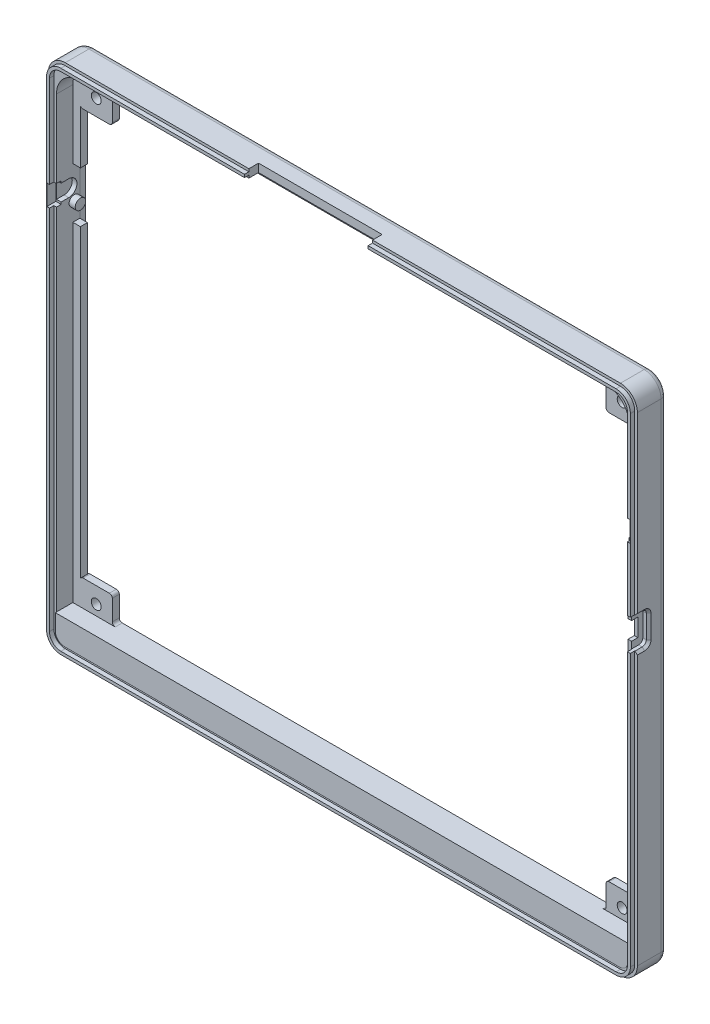
SolidWorks part; units mm, degrees
ref_plane "Спереди" through (0, 0, 0) normal (0, 0, 1) x (1, 0, 0)
ref_plane "Сверху" through (0, 0, 0) normal (0, 1, 0) x (1, 0, 0)
ref_plane "Справа" through (0, 0, 0) normal (1, 0, 0) x (0, 0, -1)
other "Configuration Table"
sketch "Perimeter_shell_profile" plane through (0, 0, 0) normal (0, 0, 1) x (1, 0, 0)
  line L0 (0, -9.8) -> (190, -9.8)
  line L1 (195.8, -4) -> (195.8, 160)
  line L2 (190, 165.8) -> (0, 165.8)
  line L3 (-5.8, 160) -> (-5.8, -4)
  line L4 (0, -7) -> (190, -7)
  line L5 (193, -4) -> (193, 160)
  line L6 (190, 163) -> (0, 163)
  line L7 (-3, 160) -> (-3, -4)
  arc A0 (190, -9.8) -> (195.8, -4) centre (190, -4) ccw
  arc A1 (195.8, 160) -> (190, 165.8) centre (190, 160) ccw
  arc A2 (0, 165.8) -> (-5.8, 160) centre (0, 160) ccw
  arc A3 (-5.8, -4) -> (0, -9.8) centre (0, -4) ccw
  arc A4 (190, -7) -> (193, -4) centre (190, -4) ccw
  arc A5 (193, 160) -> (190, 163) centre (190, 160) ccw
  arc A6 (0, 163) -> (-3, 160) centre (0, 160) ccw
  arc A7 (-3, -4) -> (0, -7) centre (0, -4) ccw
extrude "Perimeter_shell" add sketch "Perimeter_shell_profile" along normal blind 5.6 from offset 7.6 offset against normal yes
sketch "Open_back_frame_profile" plane through (0, 0, 0) normal (0, 0, 1) x (1, 0, 0)
  line L0 (0, -9.8) -> (190, -9.8)
  line L1 (195.8, -4) -> (195.8, 160)
  line L2 (190, 165.8) -> (0, 165.8)
  line L3 (-5.8, 160) -> (-5.8, -4)
  line L4 (1.6, -4.4) -> (188.4, -4.4)
  line L5 (190.4, -2.4) -> (190.4, 158.4)
  line L6 (188.4, 160.4) -> (1.6, 160.4)
  line L7 (-0.4, 158.4) -> (-0.4, -2.4)
  arc A0 (190, -9.8) -> (195.8, -4) centre (190, -4) ccw
  arc A1 (195.8, 160) -> (190, 165.8) centre (190, 160) ccw
  arc A2 (0, 165.8) -> (-5.8, 160) centre (0, 160) ccw
  arc A3 (-5.8, -4) -> (0, -9.8) centre (0, -4) ccw
  arc A4 (188.4, -4.4) -> (190.4, -2.4) centre (188.4, -2.4) ccw
  arc A5 (190.4, 158.4) -> (188.4, 160.4) centre (188.4, 158.4) ccw
  arc A6 (1.6, 160.4) -> (-0.4, 158.4) centre (1.6, 158.4) ccw
  arc A7 (-0.4, -2.4) -> (1.6, -4.4) centre (1.6, -2.4) ccw
extrude "Open_back_frame" add sketch "Open_back_frame_profile" along normal blind 4.5 from offset 12.1 offset against normal yes
sketch "PCB_mount_web_0_profile" plane through (0, 0, 0) normal (0, 0, 1) x (1, 0, 0)
  line L0 (0.5, -6) -> (9.5, -6)
  line L1 (10.5, -5) -> (10.5, 9.5)
  line L2 (9.5, 10.5) -> (0.5, 10.5)
  line L3 (-0.5, 9.5) -> (-0.5, -5)
  arc A0 (9.5, -6) -> (10.5, -5) centre (9.5, -5) ccw
  arc A1 (10.5, 9.5) -> (9.5, 10.5) centre (9.5, 9.5) ccw
  arc A2 (0.5, 10.5) -> (-0.5, 9.5) centre (0.5, 9.5) ccw
  arc A3 (-0.5, -5) -> (0.5, -6) centre (0.5, -5) ccw
extrude "PCB_mount_web_0" add sketch "PCB_mount_web_0_profile" along normal blind 4.5 from offset 12.1 offset against normal yes
sketch "PCB_M3_through_0_profile" plane through (0, 0, 0) normal (0, 0, 1) x (1, 0, 0)
  circle A0 centre (5, 5) radius 1.7
extrude "PCB_M3_through_0" cut sketch "PCB_M3_through_0_profile" against normal blind 4.7 from offset 7.5 offset against normal yes
sketch "PCB_mount_web_1_profile" plane through (0, 0, 0) normal (0, 0, 1) x (1, 0, 0)
  line L0 (180.5, -6) -> (189.5, -6)
  line L1 (190.5, -5) -> (190.5, 9.5)
  line L2 (189.5, 10.5) -> (180.5, 10.5)
  line L3 (179.5, 9.5) -> (179.5, -5)
  arc A0 (189.5, -6) -> (190.5, -5) centre (189.5, -5) ccw
  arc A1 (190.5, 9.5) -> (189.5, 10.5) centre (189.5, 9.5) ccw
  arc A2 (180.5, 10.5) -> (179.5, 9.5) centre (180.5, 9.5) ccw
  arc A3 (179.5, -5) -> (180.5, -6) centre (180.5, -5) ccw
extrude "PCB_mount_web_1" add sketch "PCB_mount_web_1_profile" along normal blind 4.5 from offset 12.1 offset against normal yes
sketch "PCB_M3_through_1_profile" plane through (0, 0, 0) normal (0, 0, 1) x (1, 0, 0)
  circle A0 centre (185, 5) radius 1.7
extrude "PCB_M3_through_1" cut sketch "PCB_M3_through_1_profile" against normal blind 4.7 from offset 7.5 offset against normal yes
sketch "PCB_mount_web_2_profile" plane through (0, 0, 0) normal (0, 0, 1) x (1, 0, 0)
  line L0 (0.5, 149.5) -> (9.5, 149.5)
  line L1 (10.5, 150.5) -> (10.5, 161)
  line L2 (9.5, 162) -> (0.5, 162)
  line L3 (-0.5, 161) -> (-0.5, 150.5)
  arc A0 (9.5, 149.5) -> (10.5, 150.5) centre (9.5, 150.5) ccw
  arc A1 (10.5, 161) -> (9.5, 162) centre (9.5, 161) ccw
  arc A2 (0.5, 162) -> (-0.5, 161) centre (0.5, 161) ccw
  arc A3 (-0.5, 150.5) -> (0.5, 149.5) centre (0.5, 150.5) ccw
extrude "PCB_mount_web_2" add sketch "PCB_mount_web_2_profile" along normal blind 4.5 from offset 12.1 offset against normal yes
sketch "PCB_M3_through_2_profile" plane through (0, 0, 0) normal (0, 0, 1) x (1, 0, 0)
  circle A0 centre (5, 155) radius 1.7
extrude "PCB_M3_through_2" cut sketch "PCB_M3_through_2_profile" against normal blind 4.7 from offset 7.5 offset against normal yes
sketch "PCB_mount_web_3_profile" plane through (0, 0, 0) normal (0, 0, 1) x (1, 0, 0)
  line L0 (180.5, 149.5) -> (189.5, 149.5)
  line L1 (190.5, 150.5) -> (190.5, 161)
  line L2 (189.5, 162) -> (180.5, 162)
  line L3 (179.5, 161) -> (179.5, 150.5)
  arc A0 (189.5, 149.5) -> (190.5, 150.5) centre (189.5, 150.5) ccw
  arc A1 (190.5, 161) -> (189.5, 162) centre (189.5, 161) ccw
  arc A2 (180.5, 162) -> (179.5, 161) centre (180.5, 161) ccw
  arc A3 (179.5, 150.5) -> (180.5, 149.5) centre (180.5, 150.5) ccw
extrude "PCB_mount_web_3" add sketch "PCB_mount_web_3_profile" along normal blind 4.5 from offset 12.1 offset against normal yes
sketch "PCB_M3_through_3_profile" plane through (0, 0, 0) normal (0, 0, 1) x (1, 0, 0)
  circle A0 centre (185, 155) radius 1.7
extrude "PCB_M3_through_3" cut sketch "PCB_M3_through_3_profile" against normal blind 4.7 from offset 7.5 offset against normal yes
sketch "Rear_glass_seat_profile" plane through (0, 0, 0) normal (0, 0, 1) x (1, 0, 0)
  line L0 (0, -7.25) -> (190, -7.25)
  line L1 (193.25, -4) -> (193.25, 160)
  line L2 (190, 163.25) -> (0, 163.25)
  line L3 (-3.25, 160) -> (-3.25, -4)
  arc A0 (190, -7.25) -> (193.25, -4) centre (190, -4) ccw
  arc A1 (193.25, 160) -> (190, 163.25) centre (190, 160) ccw
  arc A2 (0, 163.25) -> (-3.25, 160) centre (0, 160) ccw
  arc A3 (-3.25, -4) -> (0, -7.25) centre (0, -4) ccw
extrude "Rear_glass_seat" cut sketch "Rear_glass_seat_profile" against normal blind 2.2 from offset 10 offset against normal yes
sketch "PCB_lower_edge_web_profile" plane through (0, 0, 0) normal (0, 0, 1) x (1, 0, 0)
  line L0 (-0.5, -6.8) -> (190.5, -6.8)
  line L1 (190.5, -6.8) -> (190.5, 1.5)
  line L2 (190.5, 1.5) -> (-0.5, 1.5)
  line L3 (-0.5, 1.5) -> (-0.5, -6.8)
extrude "PCB_lower_edge_web" add sketch "PCB_lower_edge_web_profile" along normal blind 8.4 from offset 10 offset against normal yes
fillet "PCB_support_root_round" radius 1 2 edges at (179.5, 1.5, -8.8) (10.5, 1.5, -8.8)
sketch "Locating_tongue_profile" plane through (0, 0, 0) normal (0, 0, 1) x (1, 0, 0)
  line L0 (0, -8.9) -> (190, -8.9)
  line L1 (194.9, -4) -> (194.9, 160)
  line L2 (190, 164.9) -> (0, 164.9)
  line L3 (-4.9, 160) -> (-4.9, -4)
  line L4 (0, -7.9) -> (190, -7.9)
  line L5 (193.9, -4) -> (193.9, 160)
  line L6 (190, 163.9) -> (0, 163.9)
  line L7 (-3.9, 160) -> (-3.9, -4)
  arc A0 (190, -8.9) -> (194.9, -4) centre (190, -4) ccw
  arc A1 (194.9, 160) -> (190, 164.9) centre (190, 160) ccw
  arc A2 (0, 164.9) -> (-4.9, 160) centre (0, 160) ccw
  arc A3 (-4.9, -4) -> (0, -8.9) centre (0, -4) ccw
  arc A4 (190, -7.9) -> (193.9, -4) centre (190, -4) ccw
  arc A5 (193.9, 160) -> (190, 163.9) centre (190, 160) ccw
  arc A6 (0, 163.9) -> (-3.9, 160) centre (0, 160) ccw
  arc A7 (-3.9, -4) -> (0, -7.9) centre (0, -4) ccw
extrude "Locating_tongue" add sketch "Locating_tongue_profile" along normal blind 1.5 from offset 2 offset against normal yes
sketch "Top_connector_access_profile" plane through (0, 0, 0) normal (0, 0, 1) x (1, 0, 0)
  line L0 (62.8501, 153.5) -> (105.1501, 153.5)
  line L1 (105.1501, 153.5) -> (105.1501, 166.8)
  line L2 (105.1501, 166.8) -> (62.8501, 166.8)
  line L3 (62.8501, 166.8) -> (62.8501, 153.5)
extrude "Top_connector_access" cut sketch "Top_connector_access_profile" against normal blind 19.6 from offset 14.3
sketch "Power_retaining_web_profile" plane through (0, 0, 0) normal (0, 0, 1) x (1, 0, 0)
  line L0 (192.6, 87.5) -> (193.2, 87.5)
  line L1 (193.2, 87.5) -> (193.2, 101)
  line L2 (193.2, 101) -> (192.6, 101)
  line L3 (192.6, 101) -> (192.6, 87.5)
extrude "Power_retaining_web" add sketch "Power_retaining_web_profile" along normal blind 3.85 from offset 5.85 offset against normal yes
sketch "Slider_slot_profile" plane through (0, 0, 0) normal (0, 0, 1) x (1, 0, 0)
  line L0 (189.2, 91.22) -> (197, 91.22)
  line L1 (197, 91.22) -> (197, 97.32)
  line L2 (197, 97.32) -> (189.2, 97.32)
  line L3 (189.2, 97.32) -> (189.2, 91.22)
extrude "Slider_slot" cut sketch "Slider_slot_profile" against normal blind 3.8 from offset 0.35 offset against normal yes
sketch "Power_thumb_recess_profile" plane through (0, 0, 0) normal (1, 0, 0) x (0, 0, -1)
  line L0 (5.85, 90.32) -> (5.85, 98.22)
  line L1 (4.45, 99.62) -> (0.05, 99.62)
  line L2 (-1.35, 98.22) -> (-1.35, 90.32)
  line L3 (0.05, 88.92) -> (4.45, 88.92)
  arc A0 (5.85, 98.22) -> (4.45, 99.62) centre (4.45, 98.22) ccw
  arc A1 (0.05, 99.62) -> (-1.35, 98.22) centre (0.05, 98.22) ccw
  arc A2 (-1.35, 90.32) -> (0.05, 88.92) centre (0.05, 90.32) ccw
  arc A3 (4.45, 88.92) -> (5.85, 90.32) centre (4.45, 90.32) ccw
extrude "Power_thumb_recess" cut sketch "Power_thumb_recess_profile" along normal blind 3.4 from offset 193.8
ref_plane "Power_recess_bevel_plane_0" through (195, 0, 0) normal (1, 0, 0) x (0, 0, -1)
sketch "Power_recess_bevel_section_0" plane through (195, 0, 0) normal (1, 0, 0) x (0, 0, -1)
  line L0 (5.85, 90.32) -> (5.85, 98.22)
  line L1 (4.45, 99.62) -> (0.05, 99.62)
  line L2 (-1.35, 98.22) -> (-1.35, 90.32)
  line L3 (0.05, 88.92) -> (4.45, 88.92)
  arc A0 (5.85, 98.22) -> (4.45, 99.62) centre (4.45, 98.22) ccw
  arc A1 (0.05, 99.62) -> (-1.35, 98.22) centre (0.05, 98.22) ccw
  arc A2 (-1.35, 90.32) -> (0.05, 88.92) centre (0.05, 90.32) ccw
  arc A3 (4.45, 88.92) -> (5.85, 90.32) centre (4.45, 90.32) ccw
ref_plane "Power_recess_bevel_plane_1" through (195.8, 0, 0) normal (1, 0, 0) x (0, 0, -1)
sketch "Power_recess_bevel_section_1" plane through (195.8, 0, 0) normal (1, 0, 0) x (0, 0, -1)
  line L0 (6.65, 90.32) -> (6.65, 98.22)
  line L1 (4.45, 100.42) -> (0.05, 100.42)
  line L2 (-2.15, 98.22) -> (-2.15, 90.32)
  line L3 (0.05, 88.12) -> (4.45, 88.12)
  arc A0 (6.65, 98.22) -> (4.45, 100.42) centre (4.45, 98.22) ccw
  arc A1 (0.05, 100.42) -> (-2.15, 98.22) centre (0.05, 98.22) ccw
  arc A2 (-2.15, 90.32) -> (0.05, 88.12) centre (0.05, 90.32) ccw
  arc A3 (4.45, 88.12) -> (6.65, 90.32) centre (4.45, 90.32) ccw
loft "Power_recess_bevel" cut profiles "Power_recess_bevel_section_0", "Power_recess_bevel_section_1"
sketch "Internal_hinge_clearance_0_profile" plane through (0, 0, 0) normal (0, 0, 1) x (1, 0, 0)
  line L0 (-3, 114.2) -> (4.2, 114.2)
  line L1 (4.2, 114.2) -> (4.2, 131.6)
  line L2 (4.2, 131.6) -> (-3, 131.6)
  line L3 (-3, 131.6) -> (-3, 114.2)
extrude "Internal_hinge_clearance_0" cut sketch "Internal_hinge_clearance_0_profile" against normal blind 10.3 from offset 1.9 offset against normal yes
sketch "Internal_stop_pin_0_profile" plane through (0, 0, 0) normal (1, 0, 0) x (0, 0, -1)
  circle A0 centre (8.1134, 120.3806) radius 1.8
extrude "Internal_stop_pin_0" add sketch "Internal_stop_pin_0_profile" along normal blind 2.6 from offset 3.5 offset against normal yes
sketch "Blind_axle_bearing_0_profile" plane through (0, 0, 0) normal (1, 0, 0) x (0, 0, -1)
  circle A0 centre (6.2, 125) radius 2.8
extrude "Blind_axle_bearing_0" cut sketch "Blind_axle_bearing_0_profile" along normal blind 1.7 from offset 4.6 offset against normal yes
sketch "Axle_assembly_entry_0_profile" plane through (0, 0, 0) normal (1, 0, 0) x (0, 0, -1)
  line L0 (6.2, 122.2) -> (6.2, 127.8)
  line L1 (6.2, 127.8) -> (-0.1, 127.8)
  line L2 (-0.1, 127.8) -> (-0.1, 122.2)
  line L3 (-0.1, 122.2) -> (6.2, 122.2)
extrude "Axle_assembly_entry_0" cut sketch "Axle_assembly_entry_0_profile" along normal blind 1.7 from offset 4.6 offset against normal yes
sketch "Keeper_seat_0_profile" plane through (0, 0, 0) normal (0, 0, 1) x (1, 0, 0)
  line L0 (-4.8, 121.5) -> (-2.7, 121.5)
  line L1 (-2.7, 121.5) -> (-2.7, 128.5)
  line L2 (-2.7, 128.5) -> (-4.8, 128.5)
  line L3 (-4.8, 128.5) -> (-4.8, 121.5)
extrude "Keeper_seat_0" cut sketch "Keeper_seat_0_profile" against normal blind 3.7 from offset 0.1
sketch "Internal_hinge_clearance_1_profile" plane through (0, 0, 0) normal (0, 0, 1) x (1, 0, 0)
  line L0 (185.8, 114.2) -> (193, 114.2)
  line L1 (193, 114.2) -> (193, 131.6)
  line L2 (193, 131.6) -> (185.8, 131.6)
  line L3 (185.8, 131.6) -> (185.8, 114.2)
extrude "Internal_hinge_clearance_1" cut sketch "Internal_hinge_clearance_1_profile" against normal blind 10.3 from offset 1.9 offset against normal yes
sketch "Internal_stop_pin_1_profile" plane through (0, 0, 0) normal (1, 0, 0) x (0, 0, -1)
  circle A0 centre (8.1134, 120.3806) radius 1.8
extrude "Internal_stop_pin_1" add sketch "Internal_stop_pin_1_profile" along normal blind 2.6 from offset 190.9
sketch "Blind_axle_bearing_1_profile" plane through (0, 0, 0) normal (1, 0, 0) x (0, 0, -1)
  circle A0 centre (6.2, 125) radius 2.8
extrude "Blind_axle_bearing_1" cut sketch "Blind_axle_bearing_1_profile" along normal blind 1.7 from offset 192.9
sketch "Axle_assembly_entry_1_profile" plane through (0, 0, 0) normal (1, 0, 0) x (0, 0, -1)
  line L0 (6.2, 122.2) -> (6.2, 127.8)
  line L1 (6.2, 127.8) -> (-0.1, 127.8)
  line L2 (-0.1, 127.8) -> (-0.1, 122.2)
  line L3 (-0.1, 122.2) -> (6.2, 122.2)
extrude "Axle_assembly_entry_1" cut sketch "Axle_assembly_entry_1_profile" along normal blind 1.7 from offset 192.9
sketch "Keeper_seat_1_profile" plane through (0, 0, 0) normal (0, 0, 1) x (1, 0, 0)
  line L0 (192.7, 121.5) -> (194.8, 121.5)
  line L1 (194.8, 121.5) -> (194.8, 128.5)
  line L2 (194.8, 128.5) -> (192.7, 128.5)
  line L3 (192.7, 128.5) -> (192.7, 121.5)
extrude "Keeper_seat_1" cut sketch "Keeper_seat_1_profile" against normal blind 3.7 from offset 0.1
fillet "Outer_rear_round" radius 2 8 edges at (-4.1012, -8.1012, -12.1) (95, -9.8, -12.1) (194.1012, -8.1012, -12.1) (195.8, 78, -12.1) (194.1012, 164.1012, -12.1) (95, 165.8, -12.1) (-4.1012, 164.1012, -12.1) (-5.8, 78, -12.1)
sketch "Rear_corner_fill_0_profile" plane through (0, 0, 0) normal (0, 0, 1) x (1, 0, 0)
  line L0 (-4, -8) -> (5, -8)
  line L1 (5, -8) -> (5, 1)
  line L2 (5, 1) -> (-4, 1)
  line L3 (-4, 1) -> (-4, -8)
extrude "Rear_corner_fill_0" add sketch "Rear_corner_fill_0_profile" along normal blind 5.2 from offset 7.6 offset against normal yes
sketch "Rear_corner_radius_0_profile" plane through (0, 0, 0) normal (0, 0, 1) x (1, 0, 0)
  circle A0 centre (5, 1) radius 8
extrude "Rear_corner_radius_0" cut sketch "Rear_corner_radius_0_profile" against normal blind 5.3 from offset 2.3 offset against normal yes
sketch "Rear_corner_fill_1_profile" plane through (0, 0, 0) normal (0, 0, 1) x (1, 0, 0)
  line L0 (185, -8) -> (194, -8)
  line L1 (194, -8) -> (194, 1)
  line L2 (194, 1) -> (185, 1)
  line L3 (185, 1) -> (185, -8)
extrude "Rear_corner_fill_1" add sketch "Rear_corner_fill_1_profile" along normal blind 5.2 from offset 7.6 offset against normal yes
sketch "Rear_corner_radius_1_profile" plane through (0, 0, 0) normal (0, 0, 1) x (1, 0, 0)
  circle A0 centre (185, 1) radius 8
extrude "Rear_corner_radius_1" cut sketch "Rear_corner_radius_1_profile" against normal blind 5.3 from offset 2.3 offset against normal yes
sketch "Rear_corner_fill_2_profile" plane through (0, 0, 0) normal (0, 0, 1) x (1, 0, 0)
  line L0 (-4, 155) -> (5, 155)
  line L1 (5, 155) -> (5, 164)
  line L2 (5, 164) -> (-4, 164)
  line L3 (-4, 164) -> (-4, 155)
extrude "Rear_corner_fill_2" add sketch "Rear_corner_fill_2_profile" along normal blind 5.2 from offset 7.6 offset against normal yes
sketch "Rear_corner_radius_2_profile" plane through (0, 0, 0) normal (0, 0, 1) x (1, 0, 0)
  circle A0 centre (5, 155) radius 8
extrude "Rear_corner_radius_2" cut sketch "Rear_corner_radius_2_profile" against normal blind 5.3 from offset 2.3 offset against normal yes
sketch "Rear_corner_fill_3_profile" plane through (0, 0, 0) normal (0, 0, 1) x (1, 0, 0)
  line L0 (185, 155) -> (194, 155)
  line L1 (194, 155) -> (194, 164)
  line L2 (194, 164) -> (185, 164)
  line L3 (185, 164) -> (185, 155)
extrude "Rear_corner_fill_3" add sketch "Rear_corner_fill_3_profile" along normal blind 5.2 from offset 7.6 offset against normal yes
sketch "Rear_corner_radius_3_profile" plane through (0, 0, 0) normal (0, 0, 1) x (1, 0, 0)
  circle A0 centre (185, 155) radius 8
extrude "Rear_corner_radius_3" cut sketch "Rear_corner_radius_3_profile" against normal blind 5.3 from offset 2.3 offset against normal yes
sketch "Corner_lower_PCB_support_profile" plane through (0, 0, 0) normal (0, 0, 1) x (1, 0, 0)
  line L0 (-0.5, -6.8) -> (190.5, -6.8)
  line L1 (190.5, -6.8) -> (190.5, 1.5)
  line L2 (190.5, 1.5) -> (-0.5, 1.5)
  line L3 (-0.5, 1.5) -> (-0.5, -6.8)
extrude "Corner_lower_PCB_support" add sketch "Corner_lower_PCB_support_profile" along normal blind 8.4 from offset 10 offset against normal yes
sketch "Rear_corner_fill_0_edge_flush_profile" plane through (0, 0, 0) normal (0, 0, 1) x (1, 0, 0)
  line L0 (-4, -8) -> (5, -8)
  line L1 (5, -8) -> (5, 1)
  line L2 (5, 1) -> (-4, 1)
  line L3 (-4, 1) -> (-4, -8)
extrude "Rear_corner_fill_0_edge_flush" add sketch "Rear_corner_fill_0_edge_flush_profile" along normal blind 5.6 from offset 7.6 offset against normal yes
sketch "Rear_corner_radius_0_edge_flush_profile" plane through (0, 0, 0) normal (0, 0, 1) x (1, 0, 0)
  circle A0 centre (5, 1) radius 8
extrude "Rear_corner_radius_0_edge_flush" cut sketch "Rear_corner_radius_0_edge_flush_profile" against normal blind 5.7 from offset 1.9 offset against normal yes
sketch "Rear_corner_fill_1_edge_flush_profile" plane through (0, 0, 0) normal (0, 0, 1) x (1, 0, 0)
  line L0 (185, -8) -> (194, -8)
  line L1 (194, -8) -> (194, 1)
  line L2 (194, 1) -> (185, 1)
  line L3 (185, 1) -> (185, -8)
extrude "Rear_corner_fill_1_edge_flush" add sketch "Rear_corner_fill_1_edge_flush_profile" along normal blind 5.6 from offset 7.6 offset against normal yes
sketch "Rear_corner_radius_1_edge_flush_profile" plane through (0, 0, 0) normal (0, 0, 1) x (1, 0, 0)
  circle A0 centre (185, 1) radius 8
extrude "Rear_corner_radius_1_edge_flush" cut sketch "Rear_corner_radius_1_edge_flush_profile" against normal blind 5.7 from offset 1.9 offset against normal yes
sketch "Rear_corner_fill_2_edge_flush_profile" plane through (0, 0, 0) normal (0, 0, 1) x (1, 0, 0)
  line L0 (-4, 155) -> (5, 155)
  line L1 (5, 155) -> (5, 164)
  line L2 (5, 164) -> (-4, 164)
  line L3 (-4, 164) -> (-4, 155)
extrude "Rear_corner_fill_2_edge_flush" add sketch "Rear_corner_fill_2_edge_flush_profile" along normal blind 5.6 from offset 7.6 offset against normal yes
sketch "Rear_corner_radius_2_edge_flush_profile" plane through (0, 0, 0) normal (0, 0, 1) x (1, 0, 0)
  circle A0 centre (5, 155) radius 8
extrude "Rear_corner_radius_2_edge_flush" cut sketch "Rear_corner_radius_2_edge_flush_profile" against normal blind 5.7 from offset 1.9 offset against normal yes
sketch "Rear_corner_fill_3_edge_flush_profile" plane through (0, 0, 0) normal (0, 0, 1) x (1, 0, 0)
  line L0 (185, 155) -> (194, 155)
  line L1 (194, 155) -> (194, 164)
  line L2 (194, 164) -> (185, 164)
  line L3 (185, 164) -> (185, 155)
extrude "Rear_corner_fill_3_edge_flush" add sketch "Rear_corner_fill_3_edge_flush_profile" along normal blind 5.6 from offset 7.6 offset against normal yes
sketch "Rear_corner_radius_3_edge_flush_profile" plane through (0, 0, 0) normal (0, 0, 1) x (1, 0, 0)
  circle A0 centre (185, 155) radius 8
extrude "Rear_corner_radius_3_edge_flush" cut sketch "Rear_corner_radius_3_edge_flush_profile" against normal blind 5.7 from offset 1.9 offset against normal yes
sketch "PCB_support_edge_finish_profile" plane through (0, 0, 0) normal (0, 0, 1) x (1, 0, 0)
  line L0 (193, 1.5) -> (-3, 1.5)
  line L1 (-3, 1.5) -> (-3, -4)
  line L2 (0, -7) -> (190, -7)
  line L3 (193, -4) -> (193, 1.5)
  arc A0 (-3, -4) -> (0, -7) centre (0, -4) ccw
  arc A1 (190, -7) -> (193, -4) centre (190, -4) ccw
extrude "PCB_support_edge_finish" add sketch "PCB_support_edge_finish_profile" along normal blind 8.4 from offset 10 offset against normal yes
